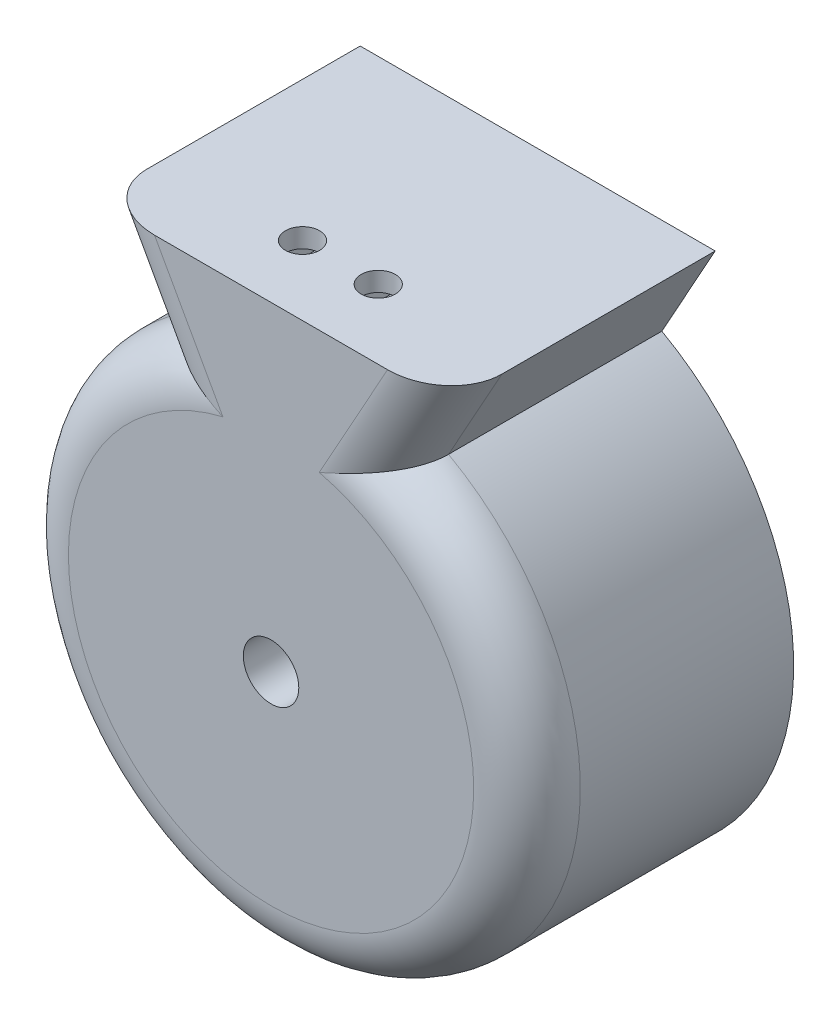
SolidWorks part; units mm, degrees
ref_plane "Front Plane" through (0, 0, 0) normal (0, 0, 1) x (1, 0, 0)
ref_plane "Top Plane" through (0, 0, 0) normal (0, 1, 0) x (1, 0, 0)
ref_plane "Right Plane" through (0, 0, 0) normal (1, 0, 0) x (0, 0, -1)
sketch "Sketch1" plane through (0, 0, 0) normal (0, 0, 1) x (1, 0, 0)
  line L0 (0, 0) -> (-16.6425, 30) construction
  line L1 (0, 0) -> (16.6425, 30) construction
  line L2 (-16.6425, 30) -> (16.6425, 30)
  line L3 (-16.6425, 30) -> (-11.6425, 20.9869)
  line L4 (16.6425, 30) -> (11.6425, 20.9869)
  arc A0 (-11.6425, 20.9869) -> (11.6425, 20.9869) centre (0, 0) ccw
  dimension "D1" = 24
  dimension "D2" = 30
  dimension "D3" = 5
extrude "Boss-Extrude1" add sketch "Sketch1" along normal blind 25
fillet "Fillet1" radius 5 3 edges at (0, -24, 25) (-14.1425, 25.4935, 25) (14.1425, 25.4935, 25)
sketch "Sketch2" plane through (0, 0, 0) normal (0, 0, 1) x (1, 0, 0)
  circle A0 centre (0, 0) radius 2.6
  dimension "D1" = 5.2
extrude "Cut-Extrude1" cut sketch "Sketch2" along normal through all
sketch "Sketch3" plane through (0, 0, 0) normal (0, 0, 1) x (1, 0, 0)
  line L0 (0, 40.26) -> (0, 0) construction
  line L2 (21.2, 65.9212) -> (-21.2, 65.9212)
  line L3 (21.2, 65.9212) -> (21.2, 23.5212)
  line L4 (21.2, 23.5212) -> (-21.2, 23.5212)
  line L5 (-21.2, 65.9212) -> (-21.2, 23.5212)
  line L6 (21.2, 65.9212) -> (-21.2, 23.5212) construction
  line L7 (21.2, 23.5212) -> (-21.2, 65.9212) construction
  point P3 (0, 44.7212)
  dimension "D1" = 42.4
  dimension "D2" = 42.4
sketch "Sketch4" plane through (0, 0, 0) normal (0, 0, 1) x (1, 0, 0)
  circle A0 centre (0, 0) radius 20
  circle A1 centre (0, 0) radius 7.5
  dimension "D1" = 40
  dimension "D2" = 15
extrude "Cut-Extrude2" cut sketch "Sketch4" along normal blind 21
sketch "Sketch5" plane through (0, 0, 0) normal (0, 1, 0) x (1, 0, 0)
  line L0 (0, 0) -> (0, -43.8459) construction
  circle A0 centre (-3.55, -18.5) radius 1.6
  circle A1 centre (3.55, -18.5) radius 1.6
  point P7 (0, 0)
  dimension "D1" = 3.2
  dimension "D2" = 3.2
  dimension "D3" = 7.1
  dimension "D4" = 3.55
  dimension "D5" = 18.5
extrude "Cut-Extrude3" cut sketch "Sketch5" against normal blind 6 from surface starting at face at (0, 30, 15.3452)
sketch "Sketch6" plane through (0, 0, 0) normal (0, 0, 1) x (1, 0, 0)
  line L0 (16.4997, 27) -> (-17.1164, 27) construction
  line L1 (6.35, 25.8) -> (0.75, 25.8)
  line L2 (6.35, 25.8) -> (6.35, 28.2)
  line L3 (6.35, 28.2) -> (0.75, 28.2)
  line L4 (0.75, 25.8) -> (0.75, 28.2)
  line L5 (6.35, 25.8) -> (0.75, 28.2) construction
  line L6 (6.35, 28.2) -> (0.75, 25.8) construction
  line L7 (-0.75, 25.8) -> (-6.35, 25.8)
  line L8 (-0.75, 25.8) -> (-0.75, 28.2)
  line L9 (-0.75, 28.2) -> (-6.35, 28.2)
  line L10 (-6.35, 25.8) -> (-6.35, 28.2)
  line L11 (-0.75, 25.8) -> (-6.35, 28.2) construction
  line L12 (-0.75, 28.2) -> (-6.35, 25.8) construction
  line L13 (0, 0) -> (0, 58.8701) construction
  point P0 (3.55, 27)
  point P5 (-3.55, 27)
  point P10 (0, 0)
  point P16 (0, 0)
  dimension "D7" = 27
  dimension "D1" = 2.4
  dimension "D2" = 5.6
  dimension "D3" = 2.4
  dimension "D4" = 5.6
  dimension "D5" = 7.1
  dimension "D6" = 3.55
extrude "Cut-Extrude4" cut sketch "Sketch6" along normal blind 22.5
